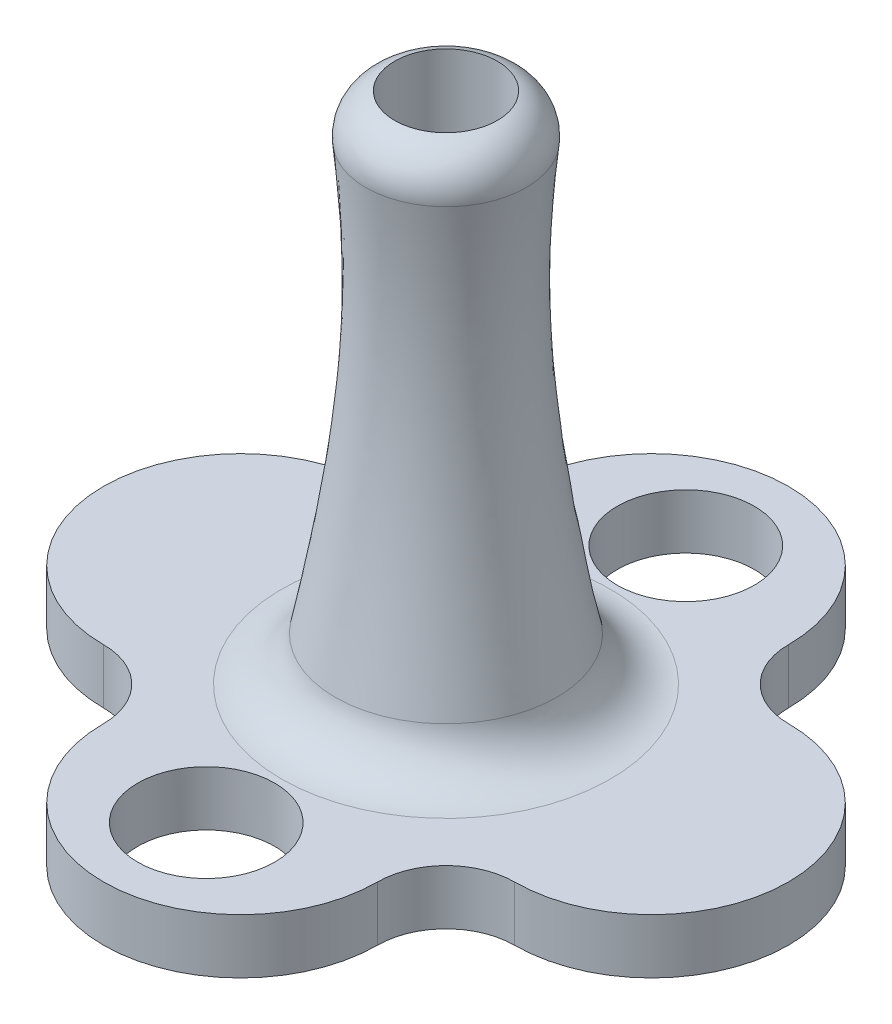
SolidWorks part; units mm, degrees
material "ABS"
ref_plane "Front Plane" through (0, 0, 0) normal (0, 0, 1) x (1, 0, 0)
ref_plane "Top Plane" through (0, 0, 0) normal (0, 1, 0) x (1, 0, 0)
ref_plane "Right Plane" through (0, 0, 0) normal (1, 0, 0) x (0, 0, -1)
sketch "Sketch1" plane through (0, 0, 0) normal (0, 1, 0) x (1, 0, 0)
  line L0 (0, -7.62) -> (0, 7.62) construction
  line L1 (-12.7, -12.7) -> (12.7, -12.7) construction
  line L2 (-12.7, -12.7) -> (-12.7, 12.7) construction
  line L3 (-12.7, 12.7) -> (12.7, 12.7) construction
  line L4 (12.7, -12.7) -> (12.7, 12.7) construction
  line L5 (-12.7, -12.7) -> (12.7, 12.7) construction
  line L6 (-12.7, 12.7) -> (12.7, -12.7) construction
  line L7 (-5.08, -7.62) -> (-5.08, -5.08)
  line L8 (5.08, -7.62) -> (5.08, -5.08)
  line L9 (-7.62, 0) -> (7.62, 0) construction
  line L10 (-7.62, 5.08) -> (-5.08, 5.08)
  line L11 (-7.62, -5.08) -> (-5.08, -5.08)
  line L12 (5.08, 5.08) -> (7.62, 5.08)
  line L13 (-5.08, 5.08) -> (-5.08, 7.62)
  line L14 (5.08, -5.08) -> (7.62, -5.08)
  line L15 (5.08, 5.08) -> (5.08, 7.62)
  arc A0 (-5.08, -7.62) -> (5.08, -7.62) centre (0, -7.62) ccw
  arc A1 (5.08, 7.62) -> (-5.08, 7.62) centre (0, 7.62) ccw
  arc A2 (-7.62, 5.08) -> (-7.62, -5.08) centre (-7.62, 0) ccw
  arc A3 (7.62, -5.08) -> (7.62, 5.08) centre (7.62, 0) ccw
  point P0 (0, 0)
  point P8 (0, 0)
  point P15 (0, 0)
  dimension "D5" = 5.08
  dimension "D8" = 5.08
  dimension "D6" = 5.08
  dimension "D7" = 5.08
  dimension "D1" = 25.4
  dimension "D2" = 25.4
  dimension "D3" = 10.16
  dimension "D4" = 10.16
extrude "Boss-Extrude1" add sketch "Sketch1" along normal blind 2.032
fillet "Fillet1" radius 2.54 4 edges at (-5.08, 1.016, -5.08) (-5.08, 1.016, 5.08) (5.08, 1.016, 5.08) (5.08, 1.016, -5.08)
sketch "Sketch2" plane through (0, 2.032, 0) normal (0, 1, 0) x (1, 0, 0)
  circle A0 centre (0, 0) radius 4.445
  dimension "D1" = 8.89
ref_plane "Plane1" through (0, 21.082, 0) normal (0, 1, 0) x (1, 0, 0)
sketch "Sketch3" plane through (0, 21.082, 0) normal (0, 1, 0) x (1, 0, 0)
  circle A0 centre (0, 0) radius 3.175
  dimension "D1" = 6.35
loft "Loft1" add profiles "Sketch2", "Sketch3" connector at (-4.4124, 2.032, 0.5377) connector at (0.018, 21.082, 3.1749)
sketch "Sketch4" plane through (0, 21.082, 0) normal (0, 1, 0) x (1, 0, 0)
  circle A0 centre (0, 0) radius 1.905
  dimension "D1" = 3.81
extrude "Cut-Extrude1" cut sketch "Sketch4" against normal up to surface (19.05 mm away) up to face at (0, 2.032, 0)
fillet "Fillet5" [suppressed] radius 1.5875 tangent propagation no
sketch "Sketch5" plane through (0, 2.032, 0) normal (0, 1, 0) x (1, 0, 0)
  line L0 (0, -16.975) -> (0, 16.975) construction
  line L1 (0, 0) -> (8.2637, 0) construction
  circle A0 centre (0, 8.89) radius 2.54
  circle A1 centre (0, 8.89) radius 3.937 construction
  arc A2 (5.08, 7.62) -> (-5.08, 7.62) centre (0, 7.62) ccw construction
  circle A3 centre (0, -8.89) radius 3.937 construction
  circle A4 centre (0, -8.89) radius 2.54
  circle A5 centre (0, 8.89) radius 2.4003 construction
  point P5 (0, 0)
  dimension "D1" = 5.08
  dimension "D2" = 7.874
  dimension "D4" = 4.8006
  dimension "D3" = 1.27
extrude "Cut-Extrude2" cut sketch "Sketch5" against normal up to surface (2.032 mm away) up to face at (0, 0, 0)
fillet "Fillet6" radius 2.032 1 edges at (0, 2.032, 4.445)
fillet "Fillet7" radius 1.524 1 edges at (0, 21.082, 3.175)
equation "\"D6@Sketch1\"=\"D8@Sketch1\""
equation "\"D7@Sketch1\"=\"D5@Sketch1\""
